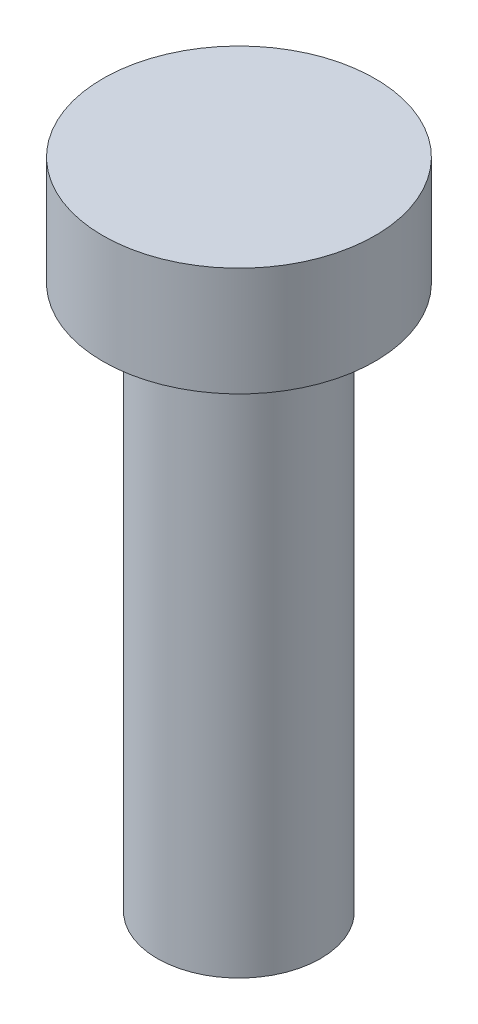
SolidWorks part; units mm, degrees
ref_plane "Front Plane" through (0, 0, 0) normal (0, 0, 1) x (1, 0, 0)
ref_plane "Top Plane" through (0, 0, 0) normal (0, 1, 0) x (1, 0, 0)
ref_plane "Right Plane" through (0, 0, 0) normal (1, 0, 0) x (0, 0, -1)
sketch "Sketch1" plane through (0, 0, 0) normal (0, 1, 0) x (1, 0, 0)
  circle A0 centre (0, 0) radius 2.5
  circle A2 centre (0, 0) radius 1.5
  dimension "D1" = 3
  dimension "D2" = 5
extrude "Boss-Extrude1" add sketch "Sketch1" along normal blind 2 contours A2 | A0 A2 region at (-2.4293, 0, 0) region at (0, 0, 0)
extrude "Boss-Extrude2" add sketch "Sketch1<3>" against normal blind 10 contours A2
sketch "Sketch1<3>" plane through (0, 0, 0) normal (0, 1, 0) x (1, 0, 0) same geometry as "Sketch1"
